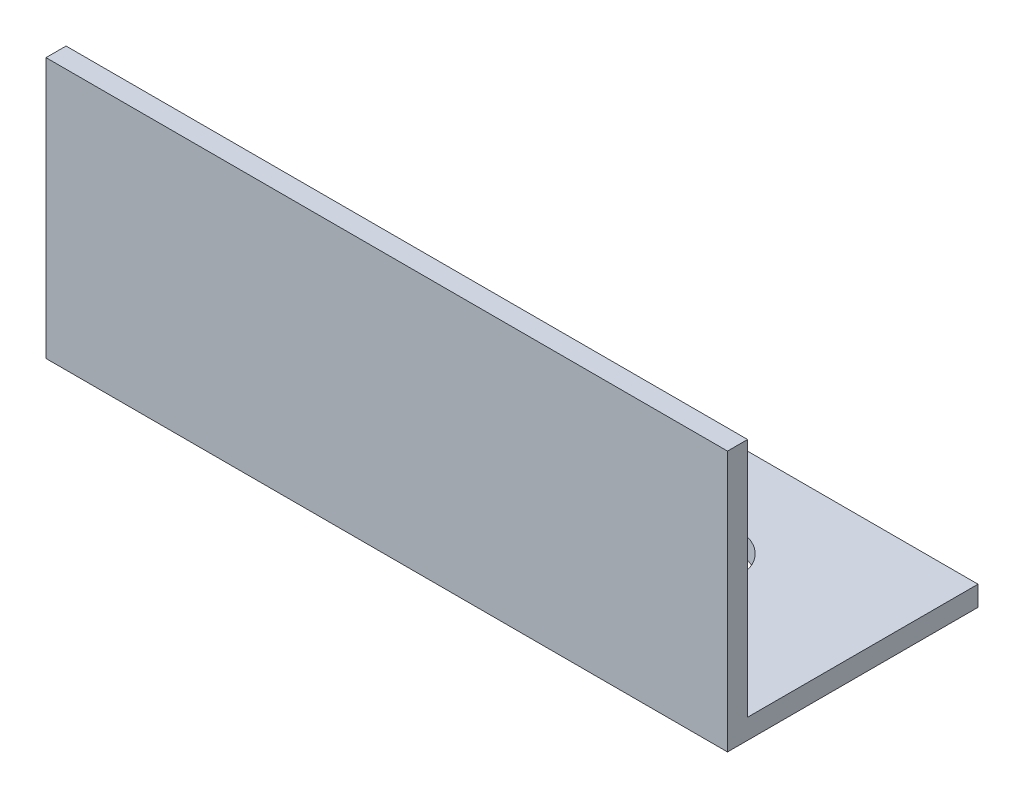
SolidWorks part; units mm, degrees
ref_plane "Front Plane" through (0, 0, 0) normal (0, 0, 1) x (1, 0, 0)
ref_plane "Top Plane" through (0, 0, 0) normal (0, 1, 0) x (1, 0, 0)
ref_plane "Right Plane" through (0, 0, 0) normal (1, 0, 0) x (0, 0, -1)
sketch "Sketch1" plane through (0, 0, 0) normal (0, 1, 0) x (1, 0, 0)
  line L0 (0, -19.05) -> (0, 19.05) construction
  line L1 (-26.99, -19.05) -> (26.99, -19.05)
  line L2 (-26.99, -19.05) -> (-26.99, 19.05)
  line L3 (-26.99, 19.05) -> (26.99, 19.05)
  line L4 (26.99, -19.05) -> (26.99, 19.05)
  line L5 (-26.99, -19.05) -> (26.99, 19.05) construction
  line L6 (-26.99, 19.05) -> (26.99, -19.05) construction
  line L7 (-26.99, 0.8) -> (26.99, 0.8)
  line L8 (-26.99, 0.8) -> (-26.99, -0.79)
  line L9 (-26.99, -0.79) -> (26.99, -0.79)
  line L10 (26.99, 0.8) -> (26.99, -0.79)
  circle A0 centre (-13.825, -10.08) radius 3.175
  circle A1 centre (13.825, -10.08) radius 3.175
  circle A2 centre (-13.825, 10.08) radius 3.175
  circle A4 centre (13.825, 10.08) radius 3.175
  point P0 (0, 0)
  dimension "D5" = 6.35
  dimension "D6" = 6.35
  dimension "D7" = 27.65
  dimension "D9" = 6.35
  dimension "D10" = 6.35
  dimension "D1" = 53.98
  dimension "D2" = 38.1
  dimension "D3" = 1.59
  dimension "D4" = 18.26
  dimension "D8" = 8.97
  dimension "D11" = 27.65
  dimension "D12" = 8.97
  dimension "D13" = 13.825
  dimension "D14" = 13.825
extrude "Boss-Extrude1" add sketch "Sketch1" along normal blind 20.64 contours L2 L9 L4 L7 region at (0, 0, -0.005)
extrude "Boss-Extrude2" add sketch "Sketch1<3>" along normal blind 1.59 contours L9 L2 L1 L4 A1 A0 | L2 L7 L4 L3 A4 A2 region at (0, 0, 9.909) region at (0, 0, -9.9143)
sketch "Sketch1<3>" plane through (0, 0, 0) normal (0, 1, 0) x (1, 0, 0) same geometry as "Sketch1"
sketch "Sketch3" plane through (0, 1.59, 0) normal (0, 1, 0) x (1, 0, 0)
  line L1 (-26.99, -0.79) -> (26.99, -0.79)
  line L2 (-26.99, -0.79) -> (-26.99, -19.05)
  line L3 (-26.99, -19.05) -> (26.99, -19.05)
  line L4 (26.99, -0.79) -> (26.99, -19.05)
extrude "Cut-Extrude1" cut sketch "Sketch3" against normal through all both and the other way through all
